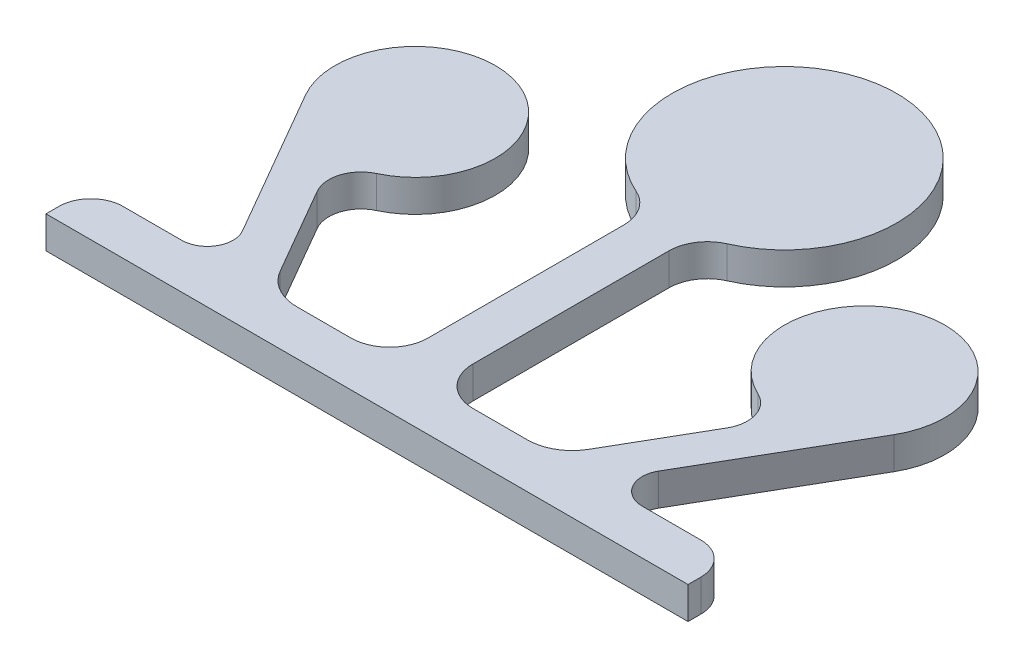
SolidWorks part; units mm, degrees
ref_plane "Спереди" through (0, 0, 0) normal (0, 0, 1) x (1, 0, 0)
ref_plane "Сверху" through (0, 0, 0) normal (0, 1, 0) x (1, 0, 0)
ref_plane "Справа" through (0, 0, 0) normal (1, 0, 0) x (0, 0, -1)
sketch "Эскиз" plane through (0, 0, 0) normal (0, 1, 0) x (1, 0, 0)
  line L0 (0, 22.5) -> (0, 27.5) construction
  line L3 (-3, 22.5) -> (-3, 27.5)
  line L4 (3, 22.5) -> (3, 27.5)
  line L5 (15.9099, 15.9099) -> (19.4454, 19.4454) construction
  line L6 (13.7886, 18.0312) -> (17.3241, 21.5668)
  line L7 (18.0312, 13.7886) -> (21.5668, 17.3241)
  line L8 (22.5, 0) -> (27.5, 0) construction
  line L9 (22.5, 3) -> (27.5, 3)
  line L10 (22.5, -3) -> (27.5, -3)
  line L11 (15.9099, -15.9099) -> (19.4454, -19.4454) construction
  line L12 (18.0312, -13.7886) -> (21.5668, -17.3241)
  line L13 (13.7886, -18.0312) -> (17.3241, -21.5668)
  line L14 (0, -22.5) -> (0, -27.5) construction
  line L15 (3, -22.5) -> (3, -27.5)
  line L16 (-3, -22.5) -> (-3, -27.5)
  line L17 (-15.9099, -15.9099) -> (-19.4454, -19.4454) construction
  line L18 (-13.7886, -18.0312) -> (-17.3241, -21.5668)
  line L19 (-18.0312, -13.7886) -> (-21.5668, -17.3241)
  line L20 (-22.5, 0) -> (-27.5, 0) construction
  line L21 (-22.5, -3) -> (-27.5, -3)
  line L22 (-22.5, 3) -> (-27.5, 3)
  line L23 (-15.9099, 15.9099) -> (-19.4454, 19.4454) construction
  line L24 (-18.0312, 13.7886) -> (-21.5668, 17.3241)
  line L25 (-13.7886, 18.0312) -> (-17.3241, 21.5668)
  line L26 (70, -20) -> (70, -70) construction
  line L27 (95, -45) -> (45, -45) construction
  line L28 (60.2192, -51.9524) -> (56.6837, -55.4879)
  line L29 (56.6837, -55.4879) -> (59.5121, -58.3163)
  line L30 (63.0476, -54.7808) -> (59.5121, -58.3163)
  line L31 (70, -45) -> (52.3223, -62.6777) construction
  line L32 (63.0476, -35.2192) -> (59.5121, -31.6837)
  line L33 (59.5121, -31.6837) -> (56.6837, -34.5121)
  line L34 (60.2192, -38.0476) -> (56.6837, -34.5121)
  line L35 (79.7808, -38.0476) -> (83.3163, -34.5121)
  line L36 (83.3163, -34.5121) -> (80.4879, -31.6837)
  line L37 (76.9524, -35.2192) -> (80.4879, -31.6837)
  line L38 (76.9524, -54.7808) -> (80.4879, -58.3163)
  line L39 (80.4879, -58.3163) -> (83.3163, -55.4879)
  line L40 (79.7808, -51.9524) -> (83.3163, -55.4879)
  line L41 (0, 0) -> (0, -116) construction
  line L42 (7, -42.9884) -> (7, -104)
  line L43 (-90, -116) -> (90, -116)
  line L44 (100, -126) -> (100, -130)
  line L45 (100, -130) -> (-100, -130)
  line L46 (91.6506, -57.5) -> (64.8038, -104)
  line L47 (63.8227, -81.6993) -> (48.0607, -109)
  line L48 (-70, -45) -> (-52.3223, -62.6777) construction
  line L49 (-95, -45) -> (-45, -45) construction
  line L50 (-70, -20) -> (-70, -70) construction
  line L51 (-79.7808, -51.9524) -> (-83.3163, -55.4879)
  line L52 (-80.4879, -58.3163) -> (-83.3163, -55.4879)
  line L53 (-76.9524, -54.7808) -> (-80.4879, -58.3163)
  line L54 (-76.9524, -35.2192) -> (-80.4879, -31.6837)
  line L55 (-83.3163, -34.5121) -> (-80.4879, -31.6837)
  line L56 (-79.7808, -38.0476) -> (-83.3163, -34.5121)
  line L57 (-60.2192, -38.0476) -> (-56.6837, -34.5121)
  line L58 (-59.5121, -31.6837) -> (-56.6837, -34.5121)
  line L59 (-63.0476, -35.2192) -> (-59.5121, -31.6837)
  line L60 (-63.0476, -54.7808) -> (-59.5121, -58.3163)
  line L61 (-56.6837, -55.4879) -> (-59.5121, -58.3163)
  line L62 (-60.2192, -51.9524) -> (-56.6837, -55.4879)
  line L63 (-63.8227, -81.6993) -> (-48.0607, -109)
  line L64 (-91.6506, -57.5) -> (-64.8038, -104)
  line L65 (-100, -126) -> (-100, -130)
  line L66 (-7, -42.9884) -> (-7, -104)
  line L68 (12.5, -7.2169) -> (0, 14.4338)
  line L69 (0, 14.4338) -> (-12.5, -7.2169)
  line L70 (-12.5, -7.2169) -> (12.5, -7.2169)
  circle A4 centre (0, 0) radius 35
  arc A5 (-3, 22.5) -> (3, 22.5) centre (0, 22.5) ccw
  arc A6 (3, 27.5) -> (-3, 27.5) centre (0, 27.5) ccw
  arc A7 (13.7886, 18.0312) -> (18.0312, 13.7886) centre (15.9099, 15.9099) ccw
  arc A8 (21.5668, 17.3241) -> (17.3241, 21.5668) centre (19.4454, 19.4454) ccw
  arc A9 (22.5, 3) -> (22.5, -3) centre (22.5, 0) ccw
  arc A10 (27.5, -3) -> (27.5, 3) centre (27.5, 0) ccw
  arc A11 (18.0312, -13.7886) -> (13.7886, -18.0312) centre (15.9099, -15.9099) ccw
  arc A12 (17.3241, -21.5668) -> (21.5668, -17.3241) centre (19.4454, -19.4454) ccw
  arc A13 (3, -22.5) -> (-3, -22.5) centre (0, -22.5) ccw
  arc A14 (-3, -27.5) -> (3, -27.5) centre (0, -27.5) ccw
  arc A15 (-13.7886, -18.0312) -> (-18.0312, -13.7886) centre (-15.9099, -15.9099) ccw
  arc A16 (-21.5668, -17.3241) -> (-17.3241, -21.5668) centre (-19.4454, -19.4454) ccw
  arc A17 (-22.5, -3) -> (-22.5, 3) centre (-22.5, 0) ccw
  arc A18 (-27.5, 3) -> (-27.5, -3) centre (-27.5, 0) ccw
  arc A19 (-18.0312, 13.7886) -> (-13.7886, 18.0312) centre (-15.9099, 15.9099) ccw
  arc A20 (-17.3241, 21.5668) -> (-21.5668, 17.3241) centre (-19.4454, 19.4454) ccw
  circle A21 centre (70, -45) radius 25
  arc A22 (58, -45) -> (60.2192, -51.9524) centre (70, -45) ccw
  arc A23 (70, -57) -> (63.0476, -54.7808) centre (70, -45) cw
  arc A24 (70, -33) -> (63.0476, -35.2192) centre (70, -45) ccw
  arc A25 (58, -45) -> (60.2192, -38.0476) centre (70, -45) cw
  arc A26 (82, -45) -> (79.7808, -38.0476) centre (70, -45) ccw
  arc A27 (70, -33) -> (76.9524, -35.2192) centre (70, -45) cw
  arc A28 (70, -57) -> (76.9524, -54.7808) centre (70, -45) ccw
  arc A29 (82, -45) -> (79.7808, -51.9524) centre (70, -45) cw
  arc A30 (90, -116) -> (100, -126) centre (90, -126) cw
  arc A31 (7, -104) -> (19, -116) centre (19, -104) ccw
  arc A32 (34.8017, -3.7204) -> (59.9417, -22.1127) centre (52.6997, -5.6338) ccw
  arc A33 (14.1489, -32.0126) -> (7, -42.9884) centre (19, -42.9884) ccw
  arc A34 (63.8227, -81.6993) -> (59.4018, -67.6424) centre (55.1625, -76.6993) ccw
  arc A35 (35.9363, -116) -> (48.0607, -109) centre (35.9363, -102) ccw
  arc A36 (64.8038, -104) -> (71.7321, -116) centre (71.7321, -108) ccw
  arc A37 (-82, -45) -> (-79.7808, -51.9524) centre (-70, -45) ccw
  arc A38 (-70, -57) -> (-76.9524, -54.7808) centre (-70, -45) cw
  arc A39 (-70, -33) -> (-76.9524, -35.2192) centre (-70, -45) ccw
  arc A40 (-82, -45) -> (-79.7808, -38.0476) centre (-70, -45) cw
  arc A41 (-58, -45) -> (-60.2192, -38.0476) centre (-70, -45) ccw
  arc A42 (-70, -33) -> (-63.0476, -35.2192) centre (-70, -45) cw
  arc A43 (-70, -57) -> (-63.0476, -54.7808) centre (-70, -45) ccw
  arc A44 (-58, -45) -> (-60.2192, -51.9524) centre (-70, -45) cw
  circle A45 centre (-70, -45) radius 25
  arc A46 (-34.8017, -3.7204) -> (-59.9417, -22.1127) centre (-52.6997, -5.6338) cw
  arc A47 (-14.1489, -32.0126) -> (-7, -42.9884) centre (-19, -42.9884) cw
  arc A48 (-64.8038, -104) -> (-71.7321, -116) centre (-71.7321, -108) cw
  arc A49 (-35.9363, -116) -> (-48.0607, -109) centre (-35.9363, -102) cw
  arc A50 (-63.8227, -81.6993) -> (-59.4018, -67.6424) centre (-55.1625, -76.6993) cw
  arc A51 (-7, -104) -> (-19, -116) centre (-19, -104) cw
  arc A52 (-90, -116) -> (-100, -126) centre (-90, -126) ccw
  circle A53 centre (0, 0) radius 7.2169 construction
  point P5 (0, 25)
  point P14 (17.6777, 17.6777)
  point P21 (25, 0)
  point P28 (17.6777, -17.6777)
  point P35 (0, -25)
  point P42 (-17.6777, -17.6777)
  point P49 (-25, 0)
  point P56 (-17.6777, 17.6777)
  point P61 (0, 0)
  point P75 (13.7886, -7.9448)
  point P90 (10.8011, -6.4946)
  point P94 (70, -45)
  point P111 (13.7886, -1.822)
  point P116 (0, 0)
  point P117 (12.7944, -3.7204)
  point P118 (14.984, 0)
  point P145 (-70, -45)
  point P169 (0, -130)
  point P170 (13.7886, -4.7525)
  point P174 (12.4325, -7.1005)
  dimension "D1" = 70
  dimension "D2" = 5
  dimension "D3" = 6
  dimension "D6" = 50
  dimension "D9" = 45
  dimension "D10" = 5
  dimension "D12" = 12
  dimension "D18" = 10
  dimension "D19" = 12
  dimension "D20" = 60
  dimension "D21" = 12
  dimension "D22" = 18
  dimension "D23" = 12
  dimension "D24" = 10
  dimension "D25" = 14
  dimension "D26" = 8
  dimension "D27" = 25
  dimension "D4" = 25
  dimension "D7" = 70
  dimension "D8" = 45
  dimension "D11" = 4
  dimension "D14" = 100
  dimension "D15" = 14
  dimension "D16" = 7
  dimension "D17" = 85
  dimension "D5" = 8
  dimension "D13" = 4
extrude "Бобышка-Вытянуть1" add sketch "Эскиз" along normal blind 10 contours A4
extrude "Бобышка-Вытянуть2" add sketch "Эскиз<7>" along normal blind 10 separate body contours A45
sketch "Эскиз<7>" plane through (0, 0, 0) normal (0, 1, 0) x (1, 0, 0) same geometry as "Эскиз"
extrude "Бобышка-Вытянуть3" add sketch "Эскиз<8>" along normal blind 10 separate body contours A21
sketch "Эскиз<8>" plane through (0, 0, 0) normal (0, 1, 0) x (1, 0, 0) same geometry as "Эскиз"
extrude "Бобышка-Вытянуть4" add sketch "Эскиз<9>" along normal blind 10 separate body contours L45 L65 A52 L43 A30 L44
sketch "Эскиз<9>" plane through (0, 0, 0) normal (0, 1, 0) x (1, 0, 0) same geometry as "Эскиз"
extrude "Бобышка-Вытянуть8" add sketch "Эскиз<21>" along normal blind 10 contours L63 A50 A45 L64 A48 L43 A49 | L66 A51 L43 A31 L42 A33 A4 A47 | A36 L46 A21 A34 L47 A35 L43 region at (0, 0, 76.4703) region at (64.7786, 0, 92.3753) region at (-64.7786, 0, 92.3753)
sketch "Эскиз<21>" plane through (0, 0, 0) normal (0, 1, 0) x (1, 0, 0) same geometry as "Эскиз"
